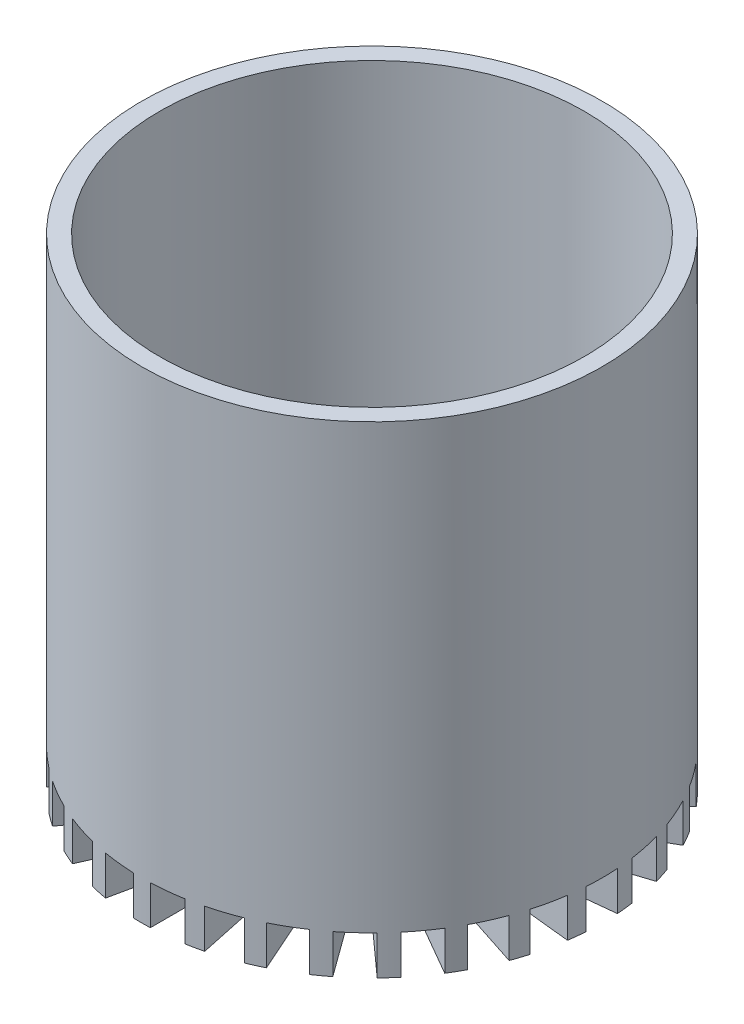
SolidWorks part; units mm, degrees
ref_plane "Front Plane" through (0, 0, 0) normal (0, 0, 1) x (1, 0, 0)
ref_plane "Top Plane" through (0, 0, 0) normal (0, 1, 0) x (1, 0, 0)
ref_plane "Right Plane" through (0, 0, 0) normal (1, 0, 0) x (0, 0, -1)
sketch "Sketch1" plane through (0, 0, 0) normal (0, 1, 0) x (1, 0, 0)
  circle A0 centre (0, 0) radius 38.1
  dimension "D1" = 76.2
extrude "Boss-Extrude1" add sketch "Sketch1" along normal blind 76.2
shell "Shell2" thickness 3.175 removed face at (0, 76.2, 38.1) outward yes
ref_axis "Axis1" through (0, 76.2, 0) along (0, -1, 0)
sketch "Sketch2" plane through (0, -3.175, 0) normal (0, -1, 0) x (-1, 0, 0)
  line L0 (0, 0) -> (0, 41.275)
  line L1 (-1.5, -41.275) -> (-1.5, 41.275)
  line L2 (-1.5, -41.275) -> (1.5, -41.275)
  line L3 (-1.5, 41.275) -> (1.5, 41.275)
  line L4 (1.5, -41.275) -> (1.5, 41.275)
  line L5 (-1.5, -41.275) -> (1.5, 41.275) construction
  line L6 (-1.5, 41.275) -> (1.5, -41.275) construction
  line L13 (-39.7184, -11.3281) -> (-38.7913, -14.1813)
  line L14 (38.7913, 14.1813) -> (39.7184, 11.3281)
  line L23 (-1.5, 41.275) -> (-1.5, -41.275)
  line L24 (1.5, 41.275) -> (1.5, -41.275)
  line L25 (1.5, 41.275) -> (-1.5, 41.275)
  line L26 (1.5, -41.275) -> (-1.5, -41.275)
  line L40 (-41.275, 1.5) -> (-41.275, -1.5)
  line L42 (41.275, 1.5) -> (41.275, -1.5)
  line L59 (1.5, 41.275) -> (1.5, -41.275)
  line L60 (1.5, 41.275) -> (-1.5, 41.275)
  line L61 (-1.5, 41.275) -> (-1.5, -41.275)
  line L62 (1.5, -41.275) -> (-1.5, -41.275)
  line L80 (41.275, -1.5) -> (41.275, 1.5)
  line L82 (-41.275, -1.5) -> (-41.275, 1.5)
  line L174 (7.1143, 40.6849) -> (-10.0488, -40.0612)
  line L175 (41.0015, -4.9753) -> (40.5322, -7.9384) [skipped]
  line L176 (-7.1143, -40.6849) -> (-10.0488, -40.0612)
  line L177 (-40.5322, 7.9384) -> (-41.0015, 4.9753) [skipped]
  line L178 (10.0488, 40.0612) -> (-7.1143, -40.6849)
  line L179 (-41.0015, 4.9753) -> (-40.5322, 7.9384) [skipped]
  line L180 (10.0488, 40.0612) -> (7.1143, 40.6849)
  line L181 (40.5322, -7.9384) -> (41.0015, -4.9753) [skipped]
  line L182 (-39.7184, 11.3281) -> (38.7913, -14.1813) [skipped]
  line L183 (39.7184, -11.3281) -> (38.7913, -14.1813) [skipped]
  line L184 (-38.7913, 14.1813) -> (39.7184, -11.3281) [skipped]
  line L185 (-38.7913, 14.1813) -> (-39.7184, 11.3281) [skipped]
  line L186 (15.4177, 38.3167) -> (-18.1584, -37.0965)
  line L187 (-15.4177, -38.3167) -> (-18.1584, -37.0965)
  line L188 (18.1584, 37.0965) -> (-15.4177, -38.3167)
  line L189 (18.1584, 37.0965) -> (15.4177, 38.3167)
  line L190 (23.0473, 34.2739) -> (-25.4744, -32.5105)
  line L191 (-23.0473, -34.2739) -> (-25.4744, -32.5105)
  line L192 (25.4744, 32.5105) -> (-23.0473, -34.2739)
  line L193 (25.4744, 32.5105) -> (23.0473, 34.2739)
  line L194 (29.6696, 28.7331) -> (-31.677, -26.5036)
  line L195 (-29.6696, -28.7331) -> (-31.677, -26.5036)
  line L196 (31.677, 26.5036) -> (-29.6696, -28.7331)
  line L197 (31.677, 26.5036) -> (29.6696, 28.7331)
  line L198 (34.9952, 21.9365) -> (-36.4952, -19.3385)
  line L199 (40.5322, 7.9384) -> (41.0015, 4.9753) [skipped]
  line L200 (-34.9952, -21.9365) -> (-36.4952, -19.3385)
  line L201 (-41.0015, -4.9753) -> (-40.5322, -7.9384) [skipped]
  line L202 (-39.7184, -11.3281) -> (38.7913, 14.1813) [skipped]
  line L203 (36.4952, 19.3385) -> (-34.9952, -21.9365)
  line L204 (-38.7913, -14.1813) -> (-39.7184, -11.3281) [skipped]
  line L205 (39.7184, 11.3281) -> (38.7913, 14.1813) [skipped]
  line L206 (-38.7913, -14.1813) -> (39.7184, 11.3281) [skipped]
  line L207 (36.4952, 19.3385) -> (34.9952, 21.9365)
  line L208 (38.7913, 14.1813) -> (-39.7184, -11.3281)
  line L209 (-38.7913, -14.1813) -> (-39.7184, -11.3281)
  line L210 (39.7184, 11.3281) -> (-38.7913, -14.1813)
  line L211 (39.7184, 11.3281) -> (38.7913, 14.1813)
  line L212 (40.8921, 5.8062) -> (-41.2057, -2.8226)
  line L213 (-40.8921, -5.8062) -> (-41.2057, -2.8226)
  line L214 (41.2057, 2.8226) -> (-40.8921, -5.8062)
  line L215 (41.2057, 2.8226) -> (40.8921, 5.8062)
  line L216 (41.2057, -2.8226) -> (-40.8921, 5.8062)
  line L217 (-41.2057, 2.8226) -> (-40.8921, 5.8062)
  line L218 (40.8921, -5.8062) -> (-41.2057, 2.8226)
  line L219 (40.8921, -5.8062) -> (41.2057, -2.8226)
  line L220 (39.7184, -11.3281) -> (-38.7913, 14.1813)
  line L221 (-39.7184, 11.3281) -> (-38.7913, 14.1813)
  line L222 (38.7913, -14.1813) -> (-39.7184, 11.3281)
  line L223 (38.7913, -14.1813) -> (39.7184, -11.3281)
  line L224 (36.4952, -19.3385) -> (-34.9952, 21.9365)
  line L225 (-36.4952, 19.3385) -> (-34.9952, 21.9365)
  line L226 (34.9952, -21.9365) -> (-36.4952, 19.3385)
  line L227 (34.9952, -21.9365) -> (36.4952, -19.3385)
  line L228 (31.677, -26.5036) -> (-29.6696, 28.7331)
  line L229 (-31.677, 26.5036) -> (-29.6696, 28.7331)
  line L230 (29.6696, -28.7331) -> (-31.677, 26.5036)
  line L231 (29.6696, -28.7331) -> (31.677, -26.5036)
  line L232 (25.4744, -32.5105) -> (-23.0473, 34.2739)
  line L233 (-25.4744, 32.5105) -> (-23.0473, 34.2739)
  line L234 (23.0473, -34.2739) -> (-25.4744, 32.5105)
  line L235 (-23.0473, -34.2739) -> (25.4744, 32.5105) [skipped]
  line L236 (23.0473, 34.2739) -> (25.4744, 32.5105) [skipped]
  line L237 (-25.4744, -32.5105) -> (23.0473, 34.2739) [skipped]
  line L238 (-25.4744, -32.5105) -> (-23.0473, -34.2739) [skipped]
  line L239 (23.0473, -34.2739) -> (25.4744, -32.5105)
  line L240 (18.1584, -37.0965) -> (-15.4177, 38.3167)
  line L241 (-18.1584, 37.0965) -> (-15.4177, 38.3167)
  line L242 (15.4177, -38.3167) -> (-18.1584, 37.0965)
  line L243 (15.4177, -38.3167) -> (18.1584, -37.0965)
  line L244 (10.0488, -40.0612) -> (-7.1143, 40.6849)
  line L245 (-10.0488, 40.0612) -> (-7.1143, 40.6849)
  line L246 (7.1143, -40.6849) -> (-10.0488, 40.0612)
  line L247 (4.9753, 41.0015) -> (-7.9384, -40.5322) [skipped]
  line L248 (-4.9753, -41.0015) -> (-7.9384, -40.5322) [skipped]
  line L249 (7.9384, 40.5322) -> (-4.9753, -41.0015) [skipped]
  line L250 (7.9384, 40.5322) -> (4.9753, 41.0015) [skipped]
  line L251 (-7.9384, -40.5322) -> (4.9753, 41.0015) [skipped]
  line L252 (4.9753, 41.0015) -> (7.9384, 40.5322) [skipped]
  line L253 (-4.9753, -41.0015) -> (7.9384, 40.5322) [skipped]
  line L254 (-7.9384, -40.5322) -> (-4.9753, -41.0015) [skipped]
  line L255 (7.9384, 40.5322) -> (-4.9753, -41.0015) [skipped]
  line L256 (-4.9753, -41.0015) -> (-7.9384, -40.5322) [skipped]
  line L257 (4.9753, 41.0015) -> (-7.9384, -40.5322) [skipped]
  line L258 (7.9384, 40.5322) -> (4.9753, 41.0015) [skipped]
  line L259 (-7.9384, -40.5322) -> (7.9384, 40.5322) construction
  line L260 (4.9753, 41.0015) -> (-4.9753, -41.0015) construction
  line L261 (-25.4744, 32.5105) -> (23.0473, -34.2739) [skipped]
  line L262 (25.4744, -32.5105) -> (23.0473, -34.2739) [skipped]
  line L263 (-23.0473, 34.2739) -> (25.4744, -32.5105) [skipped]
  line L264 (-23.0473, 34.2739) -> (-25.4744, 32.5105) [skipped]
  line L265 (7.1143, -40.6849) -> (10.0488, -40.0612)
  line L266 (1.5, -41.275) -> (1.5, 41.275)
  line L267 (-1.5, 41.275) -> (1.5, 41.275)
  line L268 (-1.5, -41.275) -> (-1.5, 41.275)
  line L269 (14.1813, -38.7913) -> (11.3281, -39.7184) [skipped]
  line L270 (-11.3281, 39.7184) -> (-14.1813, 38.7913) [skipped]
  line L271 (-1.5, -41.275) -> (1.5, -41.275)
  line L275 (-14.1813, 38.7913) -> (-11.3281, 39.7184) [skipped]
  line L276 (11.3281, -39.7184) -> (14.1813, -38.7913) [skipped]
  line L277 (0, 0) -> (6.4568, 40.7668) [skipped]
  line L278 (-41.275, -1.5) -> (41.275, -1.5) [skipped]
  line L279 (-41.275, 1.5) -> (41.275, 1.5) [skipped]
  line L280 (41.275, -1.5) -> (-41.275, -1.5) [skipped]
  line L281 (41.275, 1.5) -> (-41.275, 1.5) [skipped]
  line L331 (1.5, -41.275) -> (1.5, 41.275)
  line L332 (-1.5, 41.275) -> (1.5, 41.275)
  line L333 (-1.5, -41.275) -> (-1.5, 41.275)
  line L334 (-1.5, -41.275) -> (1.5, -41.275)
  line L335 (7.7222, 40.5739) -> (-10.6469, -39.9064) [skipped]
  line L336 (-7.7222, -40.5739) -> (-10.6469, -39.9064) [skipped]
  line L337 (10.6469, 39.9064) -> (-7.7222, -40.5739) [skipped]
  line L338 (10.6469, 39.9064) -> (7.7222, 40.5739) [skipped]
  line L339 (16.5571, 37.8383) -> (-19.26, -36.5367) [skipped]
  line L340 (-16.5571, -37.8383) -> (-19.26, -36.5367) [skipped]
  line L341 (19.26, 36.5367) -> (-16.5571, -37.8383) [skipped]
  line L342 (19.26, 36.5367) -> (16.5571, 37.8383) [skipped]
  line L343 (24.5618, 33.2053) -> (-26.9073, -31.3349) [skipped]
  line L344 (-24.5618, -33.2053) -> (-26.9073, -31.3349) [skipped]
  line L345 (26.9073, 31.3349) -> (-24.5618, -33.2053) [skipped]
  line L346 (26.9073, 31.3349) -> (24.5618, 33.2053) [skipped]
  line L347 (31.3349, 26.9073) -> (-33.2053, -24.5618) [skipped]
  line L348 (-31.3349, -26.9073) -> (-33.2053, -24.5618) [skipped]
  line L349 (33.2053, 24.5618) -> (-31.3349, -26.9073) [skipped]
  line L350 (33.2053, 24.5618) -> (31.3349, 26.9073) [skipped]
  line L351 (36.5367, 19.26) -> (-37.8383, -16.5571) [skipped]
  line L352 (-36.5367, -19.26) -> (-37.8383, -16.5571) [skipped]
  line L353 (37.8383, 16.5571) -> (-36.5367, -19.26) [skipped]
  line L354 (37.8383, 16.5571) -> (36.5367, 19.26) [skipped]
  line L355 (39.9064, 10.6469) -> (-40.5739, -7.7222) [skipped]
  line L356 (-39.9064, -10.6469) -> (-40.5739, -7.7222) [skipped]
  line L357 (40.5739, 7.7222) -> (-39.9064, -10.6469) [skipped]
  line L358 (40.5739, 7.7222) -> (39.9064, 10.6469) [skipped]
  line L359 (41.275, 1.5) -> (-41.275, 1.5) [skipped]
  line L360 (-41.275, -1.5) -> (-41.275, 1.5) [skipped]
  line L361 (41.275, -1.5) -> (-41.275, -1.5) [skipped]
  line L362 (41.275, -1.5) -> (41.275, 1.5) [skipped]
  line L363 (40.5739, -7.7222) -> (-39.9064, 10.6469) [skipped]
  line L364 (-40.5739, 7.7222) -> (-39.9064, 10.6469) [skipped]
  line L365 (39.9064, -10.6469) -> (-40.5739, 7.7222) [skipped]
  line L366 (39.9064, -10.6469) -> (40.5739, -7.7222) [skipped]
  line L367 (37.8383, -16.5571) -> (-36.5367, 19.26) [skipped]
  line L368 (-37.8383, 16.5571) -> (-36.5367, 19.26) [skipped]
  line L369 (36.5367, -19.26) -> (-37.8383, 16.5571) [skipped]
  line L370 (36.5367, -19.26) -> (37.8383, -16.5571) [skipped]
  line L371 (33.2053, -24.5618) -> (-31.3349, 26.9073) [skipped]
  line L372 (-33.2053, 24.5618) -> (-31.3349, 26.9073) [skipped]
  line L373 (31.3349, -26.9073) -> (-33.2053, 24.5618) [skipped]
  line L374 (31.3349, -26.9073) -> (33.2053, -24.5618) [skipped]
  line L375 (26.9073, -31.3349) -> (-24.5618, 33.2053) [skipped]
  line L376 (-26.9073, 31.3349) -> (-24.5618, 33.2053) [skipped]
  line L377 (24.5618, -33.2053) -> (-26.9073, 31.3349) [skipped]
  line L378 (24.5618, -33.2053) -> (26.9073, -31.3349) [skipped]
  line L379 (19.26, -36.5367) -> (-16.5571, 37.8383) [skipped]
  line L380 (-19.26, 36.5367) -> (-16.5571, 37.8383) [skipped]
  line L381 (16.5571, -37.8383) -> (-19.26, 36.5367) [skipped]
  line L382 (16.5571, -37.8383) -> (19.26, -36.5367) [skipped]
  line L383 (10.6469, -39.9064) -> (-7.7222, 40.5739) [skipped]
  line L384 (-10.6469, 39.9064) -> (-7.7222, 40.5739) [skipped]
  line L385 (7.7222, -40.5739) -> (-10.6469, 39.9064) [skipped]
  line L386 (7.7222, -40.5739) -> (10.6469, -39.9064) [skipped]
  circle A1 centre (0, 0) radius 41.275 construction
  circle A2 centre (0, 0) radius 41.275
  circle A3 centre (0, 0) radius 41.275
  dimension "D1" = 3
  dimension "D2" = 6
  dimension "D3" = 4
  dimension "D4" = 2
  dimension "D5" = 15
  dimension "D6" = 16
extrude "Boss-Extrude2" add sketch "Sketch2" along normal blind 7 contours L4 L3 L1 L2 | L174 L176 L178 L180 | L186 L187 L188 L189 | L192 L191 L190 L193 | L212 L213 L214 L215 | L194 L195 L196 L197 | L198 L200 L203 L207 | L208 L209 L210 L211 | L240 L241 L242 L243 | L232 L233 L234 L239 | L228 L229 L230 L231 | L224 L225 L226 L227 | L220 L221 L222 L223 | L216 L217 L218 L219 | L244 L245 L246 L265
sketch "Sketch3" plane through (0, -3.175, 0) normal (0, -1, 0) x (1, 0, 0)
  circle A0 centre (0, 0) radius 41.275
  circle A1 centre (0, 0) radius 61.9063
extrude "Cut-Extrude1" cut sketch "Sketch3" against normal through all both and the other way through all
sketch "Sketch4" plane through (0, -10.175, 0) normal (0, -1, 0) x (1, 0, 0)
  circle A0 centre (0, 0) radius 20.64
extrude "Cut-Extrude2" cut sketch "Sketch4" against normal up to surface (7 mm away) up to face at (-9.9713, -3.175, -30.6886)
scale "Scale1" scale about centroid uniform scaling yes scale factor 0.615385
